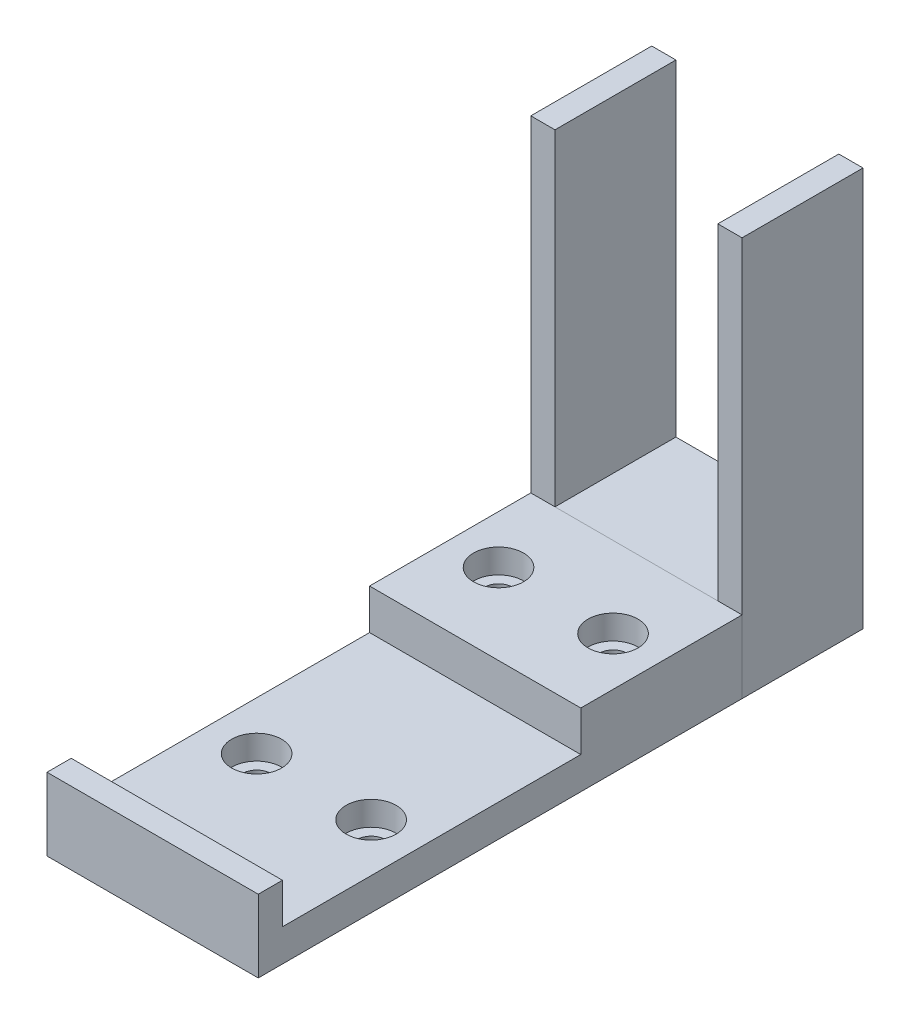
SolidWorks part; units mm, degrees
ref_plane "Alzado" through (0, 0, 0) normal (0, 0, 1) x (1, 0, 0)
ref_plane "Planta" through (0, 0, 0) normal (0, 1, 0) x (1, 0, 0)
ref_plane "Vista lateral" through (0, 0, 0) normal (1, 0, 0) x (0, 0, -1)
sketch "Croquis1" plane through (0, 0, 0) normal (0, 0, 1) x (1, 0, 0)
  line L0 (-13.1, 20.25) -> (-10.1, 20.25)
  line L1 (-10.1, -20.25) -> (10.1, -20.25)
  line L2 (-10.1, -20.25) -> (-10.1, 20.25)
  line L4 (10.1, -20.25) -> (10.1, 20.25)
  line L5 (-10.1, -20.25) -> (10.1, 20.25) construction
  line L6 (-10.1, 20.25) -> (10.1, -20.25) construction
  line L7 (-13.1, -29.25) -> (13.1, -29.25)
  line L8 (-13.1, -29.25) -> (-13.1, 20.25)
  line L10 (13.1, -29.25) -> (13.1, 20.25)
  line L11 (-13.1, -29.25) -> (9.0692, 20.25) construction
  line L12 (-9.0692, 20.25) -> (13.1, -29.25) construction
  line L13 (10.1, 20.25) -> (13.1, 20.25)
  point P0 (0, 0)
  point P6 (0, 0)
  dimension "D1" = 20.2
  dimension "D2" = 40.5
  dimension "D3" = 9
  dimension "D4" = 3
extrude "Saliente-Extruir1" add sketch "Croquis1" along normal blind 15
sketch "Croquis3" plane through (0, 0, 0) normal (0, 0, -1) x (-1, 0, 0)
  line L0 (-13.1, -29.25) -> (-13.1, 20.25) construction
  line L1 (13.1, 20.25) -> (13.1, -29.25) construction
  line L2 (-10.1, -20.25) -> (10.1, -20.25) construction
  circle A0 centre (4.7, 25.25) radius 1.75
  circle A1 centre (-4.7, 25.25) radius 1.75
  circle A2 centre (4.7, -24.75) radius 1.75
  circle A3 centre (-4.7, -24.75) radius 1.75
  dimension "D1" = 3.5
  dimension "D2" = 3.5
  dimension "D3" = 3.5
  dimension "D4" = 3.5
  dimension "D5" = 8.4
  dimension "D6" = 8.4
  dimension "D7" = 4.5
  dimension "D8" = 4.5
extrude "Cortar-Extruir1" cut sketch "Croquis3" against normal blind 12
ref_plane "Plano1" through (0, 0, 7) normal (0, 0, -1) x (-1, 0, 0)
sketch "Croquis4" plane through (0, 0, 7) normal (0, 0, -1) x (-1, 0, 0)
  line L23 (7.8, -24.75) -> (7.8, -29.25)
  line L26 (7.8, -29.25) -> (1.6, -29.25)
  line L27 (13.1, -29.25) -> (-13.1, -29.25) construction
  line L28 (1.6, -29.25) -> (1.6, -24.75)
  line L29 (-1.6, -24.75) -> (-1.6, -29.25)
  line L30 (-1.6, -29.25) -> (-7.8, -29.25)
  line L31 (-7.8, -29.25) -> (-7.8, -24.75)
  arc A6 (7.8, -24.75) -> (1.6, -24.75) centre (4.7, -24.75) ccw
  arc A7 (-1.6, -24.75) -> (-7.8, -24.75) centre (-4.7, -24.75) ccw
  dimension "D3" = 6.2
  dimension "D4" = 6.2
extrude "Cortar-Extruir2" cut sketch "Croquis4" against normal blind 3.2
sketch "Croquis6" plane through (0, 0, 15) normal (0, 0, 1) x (1, 0, 0)
  line L0 (13.1, -29.25) -> (13.1, 20.25) construction
  line L1 (-13.1, -29.25) -> (13.1, -29.25)
  line L2 (-13.1, -29.25) -> (-13.1, -20.25)
  line L3 (-13.1, -20.25) -> (13.1, -20.25)
  line L4 (13.1, -29.25) -> (13.1, -20.25)
  line L6 (-10.1, -20.25) -> (10.1, -20.25) construction
extrude "Saliente-Extruir2" add sketch "Croquis6" along normal blind 20
sketch "Croquis8" plane through (0, 0, 35) normal (0, 0, 1) x (1, 0, 0)
  line L0 (13.1, -29.25) -> (13.1, -20.25) construction
  line L1 (-13.1, -29.25) -> (13.1, -29.25)
  line L2 (-13.1, -29.25) -> (-13.1, -25.25)
  line L3 (-13.1, -25.25) -> (13.1, -25.25)
  line L4 (13.1, -29.25) -> (13.1, -25.25)
  dimension "D1" = 4
extrude "Saliente-Extruir4" add sketch "Croquis8" along normal blind 40
sketch "Croquis9" plane through (0, -25.25, 0) normal (0, 1, 0) x (1, 0, 0)
  line L0 (13.1, -75) -> (13.1, -35) construction
  line L1 (-13.1, -75) -> (13.1, -75)
  line L2 (-13.1, -75) -> (-13.1, -72)
  line L3 (-13.1, -72) -> (13.1, -72)
  line L4 (13.1, -75) -> (13.1, -72)
  dimension "D1" = 3
extrude "Saliente-Extruir5" add sketch "Croquis9" along normal blind 5
sketch "Croquis10" plane through (0, -20.25, 0) normal (0, 1, 0) x (1, 0, 0)
  line L0 (-13.1, -72) -> (-13.1, -35) construction
  line L1 (13.1, -72) -> (13.1, -35) construction
  line L2 (-13.1, -35) -> (-13.1, -15) construction
  line L3 (13.1, -35) -> (13.1, -15) construction
  line L5 (13.1, -35) -> (-13.1, -35) construction
  line L6 (13.1, -35) -> (-13.1, -35) construction
  line L7 (10.1, 0) -> (-10.1, 0) construction
  circle A0 centre (-7.1, -25) radius 1.75
  circle A1 centre (7.1, -25) radius 1.75
  circle A2 centre (-7.1, -55) radius 1.75
  circle A3 centre (7.1, -55) radius 1.75
  dimension "D1" = 3.5
  dimension "D2" = 3.5
  dimension "D3" = 3.5
  dimension "D4" = 3.5
  dimension "D5" = 6
  dimension "D6" = 6
  dimension "D7" = 6
  dimension "D8" = 6
  dimension "D9" = 25
  dimension "D10" = 25
  dimension "D11" = 20
  dimension "D12" = 20
extrude "Cortar-Extruir3" cut sketch "Croquis10" against normal through all
sketch "Croquis11" plane through (0, -20.25, 0) normal (0, 1, 0) x (1, 0, 0)
  circle A0 centre (-7.1, -25) radius 3.1
  circle A1 centre (7.1, -25) radius 3.1
  dimension "D1" = 6.2
  dimension "D2" = 6.2
extrude "Cortar-Extruir4" cut sketch "Croquis11" against normal blind 3
sketch "Croquis12" plane through (0, -25.25, 0) normal (0, 1, 0) x (1, 0, 0)
  circle A0 centre (-7.1, -55) radius 3.1
  circle A1 centre (7.1, -55) radius 3.1
  dimension "D1" = 6.2
  dimension "D2" = 6.2
extrude "Cortar-Extruir5" cut sketch "Croquis12" against normal blind 3
split "Partir1" bodies to split 111 resulting bodies 112 113 split by face at (11.6, 0, 15)
